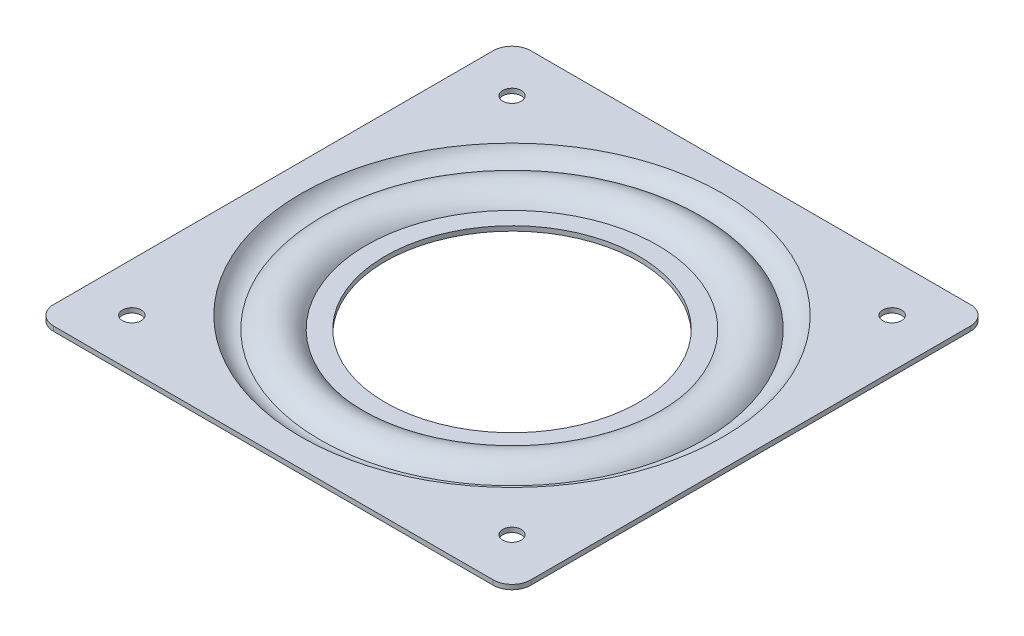
SolidWorks part; units mm, degrees
ref_plane "前视基准面" through (0, 0, 0) normal (0, 0, 1) x (1, 0, 0)
ref_plane "上视基准面" through (0, 0, 0) normal (0, 1, 0) x (1, 0, 0)
ref_plane "右视基准面" through (0, 0, 0) normal (1, 0, 0) x (0, 0, -1)
sketch "草图1" plane through (0, 0, 0) normal (0, 0, 1) x (1, 0, 0)
  line L0 (-36.7805, 0) -> (-35.9228, 0)
  line L1 (0, 6.9172) -> (0, -6.9172) construction
  line L2 (-31, -2.5698) -> (-27, -2.5698)
  line L3 (-35.9228, 0) -> (0, 0) construction
  line L4 (0, 0) -> (43.3864, 0) construction
  line L5 (-43.3864, 0) -> (-36.7805, 0) construction
  line L6 (-31.5531, -3.5698) -> (-27, -3.5698)
  line L7 (-27, -2.5698) -> (-27, -3.5698)
  line L8 (-44.9105, 0) -> (-45.8139, -0.4289)
  arc A0 (-44.9105, 0) -> (-40.8455, -2.5698) centre (-40.8455, 1.9302) ccw
  arc A1 (-40.8455, -2.5698) -> (-31, -2.5698) centre (-35.9228, -6) cw
  arc A2 (-40.8455, -2.5698) -> (-36.8127, -0.0664) centre (-40.8455, 1.9302) ccw construction
  arc A3 (-36.8127, -0.0664) -> (-36.7805, 0) centre (-40.8455, 1.9302) ccw
  arc A4 (-45.8139, -0.4289) -> (-40.2759, -3.5402) centre (-40.8455, 1.9302) ccw
  arc A5 (-40.2759, -3.5402) -> (-31.5531, -3.5698) centre (-35.9228, -6) cw
  point P4 (0, 0)
  point P8 (0, 0)
  dimension "D1" = 4.5
  dimension "D2" = 6
  dimension "D3" = 27
  dimension "D4" = 4
revolve "旋转1" add sketch "草图1" angle 360 about L1 region at (-33.2348, -0.8509, 0)
sketch "草图2" plane through (0, 0, 0) normal (0, 1, 0) x (1, 0, 0)
  line L1 (-46.8, 50.8) -> (46.8, 50.8)
  line L2 (-50.8, 46.8) -> (-50.8, -46.8)
  line L3 (-46.8, -50.8) -> (46.8, -50.8)
  line L4 (50.8, 46.8) -> (50.8, -46.8)
  line L5 (-50.8, 50.8) -> (50.8, -50.8) construction
  line L6 (-50.8, -50.8) -> (50.8, 50.8) construction
  circle A0 centre (0, 0) radius 44.9105 construction
  circle A1 centre (0, 0) radius 44.9105
  arc A2 (-46.8, 50.8) -> (-50.8, 46.8) centre (-46.8, 46.8) ccw
  circle A3 centre (-40.48, 40.48) radius 1.985
  circle A4 centre (40.48, 40.48) radius 1.985
  arc A5 (50.8, 46.8) -> (46.8, 50.8) centre (46.8, 46.8) ccw
  circle A6 centre (40.48, -40.48) radius 1.985
  arc A7 (46.8, -50.8) -> (50.8, -46.8) centre (46.8, -46.8) ccw
  circle A8 centre (-40.48, -40.48) radius 1.985
  arc A9 (-50.8, -46.8) -> (-46.8, -50.8) centre (-46.8, -46.8) ccw
  point P12 (0, 0)
  point P13 (0, 0)
  point P14 (0, 0)
  point P32 (0, 0)
  dimension "D3" = 4
  dimension "D4" = 3.97
  dimension "D5" = 4
  dimension "D1" = 90
  dimension "D2" = 101.6
  dimension "D6" = 57.2474
extrude "凸台-拉伸1" add sketch "草图2" against normal blind 1 contours L2 L3 L4 L1 A2 A3 A1 region at (0, 0, -49.3632)
